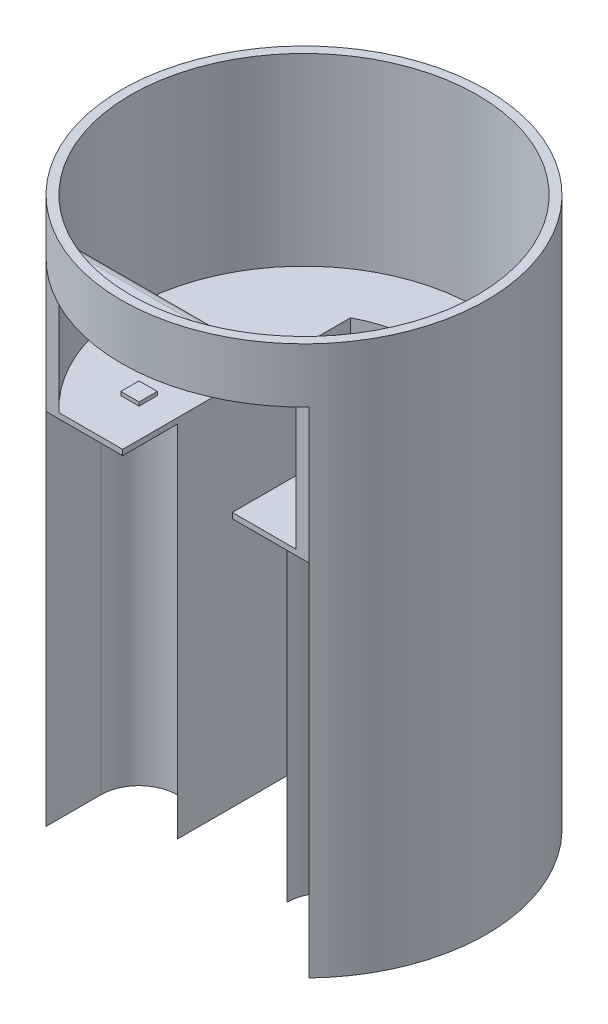
SolidWorks part; units mm, degrees
ref_plane "Front Plane" through (0, 0, 0) normal (0, 0, 1) x (1, 0, 0)
ref_plane "Top Plane" through (0, 0, 0) normal (0, 1, 0) x (1, 0, 0)
ref_plane "Right Plane" through (0, 0, 0) normal (1, 0, 0) x (0, 0, -1)
sketch "Sketch2" plane through (0, 0, 0) normal (0, 1, 0) x (1, 0, 0)
  line L0 (0.0632, -6.4631) -> (0.0632, -55.8981) construction
  line L1 (-29.9368, 95.4138) -> (-29.9368, -39.463)
  line L2 (30.0632, 95.374) -> (30.0632, -39.463)
  line L3 (-71.9368, -39.463) -> (-71.9368, -69.463)
  line L4 (72.0632, -39.463) -> (72.0632, -69.463)
  arc A0 (72.0632, -69.3317) -> (30.0632, 95.374) centre (0, 0) ccw
  arc A1 (-29.9368, -39.463) -> (-71.9368, -39.463) centre (-50.9368, -39.463) ccw
  arc A2 (30.0632, -39.463) -> (72.0632, -39.463) centre (51.0632, -39.463) cw
  arc A3 (-29.9368, 95.4138) -> (-71.9368, -69.463) centre (0, 0) ccw
  dimension "D1" = 100
  dimension "D5" = 42
  dimension "D2" = 30
  dimension "D3" = 164.8768
  dimension "D6" = 30
extrude "Boss-Extrude2" add sketch "Sketch2" along normal blind 200 contours L1 A3 L3 A1 | L2 A2 L4 A0 region at (-62.4571, 0, -19.5366) region at (62.5169, 0, -19.5555)
sketch "Sketch3" plane through (0, 200, 0) normal (0, 1, 0) x (1, 0, 0)
  line L0 (-71.9368, -69.463) -> (-29.9368, -69.463)
  line L1 (-29.9368, -69.463) -> (-29.9368, -39.463)
  line L3 (-55.9368, -34.463) -> (-45.9368, -34.463)
  line L4 (-55.9368, -34.463) -> (-55.9368, -44.463)
  line L5 (-55.9368, -44.463) -> (-45.9368, -44.463)
  line L6 (-45.9368, -34.463) -> (-45.9368, -44.463)
  line L7 (-55.9368, -34.463) -> (-45.9368, -44.463) construction
  line L8 (-55.9368, -44.463) -> (-45.9368, -34.463) construction
  point P3 (-50.9368, -39.463)
  line M7 (-71.9368, -69.463) -> (-71.9368, -39.463)
  arc M8 (-71.9368, -39.463) -> (-29.9368, -39.463) centre (-50.9368, -39.463) cw
  dimension "D1" = 10
extrude "Boss-Extrude3" add sketch "Sketch3" along direction (0, -1, 0) on the side against the normal blind 3 contours L0 L1 L3 L6 L5 L4 M8 M7 region at (-50.9368, 200, 46.3318)
sketch "Sketch4" plane through (0, 200, 0) normal (0, 1, 0) x (1, 0, 0)
  line L0 (72.0632, -69.3317) -> (30.0632, -69.3317)
  line L1 (30.0632, -39.463) -> (30.0632, -69.3317)
  line L3 (46.0632, -34.463) -> (56.0632, -34.463)
  line L4 (46.0632, -34.463) -> (46.0632, -44.463)
  line L5 (46.0632, -44.463) -> (56.0632, -44.463)
  line L6 (56.0632, -34.463) -> (56.0632, -44.463)
  line L7 (46.0632, -34.463) -> (56.0632, -44.463) construction
  line L8 (46.0632, -44.463) -> (56.0632, -34.463) construction
  point P1 (51.0632, -39.463)
  arc M6 (30.0632, -39.463) -> (72.0632, -39.463) centre (51.0632, -39.463) cw
  line M7 (72.0632, -39.463) -> (72.0632, -69.3317)
  dimension "D1" = 10
extrude "Boss-Extrude4" add sketch "Sketch4" against normal blind 3 contours L1 L0 L3 L6 L5 L4 M6 M7 region at (51.0632, 200, 46.263)
sketch "Sketch5" plane through (0, 200, 0) normal (0, 1, 0) x (1, 0, 0)
  line L1 (-55.9368, -34.463) -> (-45.9368, -34.463)
  line L2 (-55.9368, -34.463) -> (-55.9368, -44.463)
  line L3 (-55.9368, -44.463) -> (-45.9368, -44.463)
  line L4 (-45.9368, -34.463) -> (-45.9368, -44.463)
  line L5 (46.0632, -34.463) -> (56.0632, -34.463)
  line L6 (46.0632, -34.463) -> (46.0632, -44.463)
  line L7 (46.0632, -44.463) -> (56.0632, -44.463)
  line L8 (56.0632, -34.463) -> (56.0632, -44.463)
extrude "Boss-Extrude5" add sketch "Sketch5" along normal blind 2 separate body contours L8 L5 L6 L7 | L2 L1 L4 L3 region at (51.0632, 200, 39.463)
sketch "Sketch7" plane through (0, 200, 0) normal (0, 1, 0) x (1, 0, 0)
  line L0 (-29.9368, 95.4138) -> (-29.9368, 55.4328)
  line L2 (30.0632, 95.374) -> (30.0632, 55.3643)
  arc A0 (30.0632, 95.374) -> (-29.9368, 95.4138) centre (0, 0) ccw
  arc A1 (30.0632, 55.3643) -> (-29.9368, 55.4328) centre (0, 0) ccw
  dimension "D1" = 126
  dimension "D2" = 40.0097
  dimension "D3" = 39.981
extrude "Boss-Extrude6" add sketch "Sketch7" against normal up to surface (200 mm away) contours A1 L0 A0 L2 up to face at (-62.4289, 0, 5.0663)
sketch "Sketch8" plane through (0, 200, 0) normal (0, 1, 0) x (1, 0, 0)
  line L0 (-71.9368, -69.463) -> (-64.8066, -69.463)
  line L2 (72.0632, -69.3317) -> (64.947, -69.3317)
  arc A0 (72.0632, -69.3317) -> (-71.9368, -69.463) centre (0, 0) ccw
  arc A1 (64.947, -69.3317) -> (-64.8066, -69.463) centre (0, 0) ccw
  dimension "D1" = 7.1301
  dimension "D2" = 190
  dimension "D3" = 7.1163
extrude "Boss-Extrude7" add sketch "Sketch8" along normal blind 101 contours A1 L0 A0 L2
sketch "Sketch10" plane through (0, 301, 0) normal (0, 1, 0) x (1, 0, 0)
  line L0 (-71.9368, -69.463) -> (-64.8066, -69.463)
  line L1 (64.947, -69.3317) -> (72.0632, -69.3317)
  arc A0 (-71.9368, -69.463) -> (72.0632, -69.3317) centre (0, 0) ccw
  arc A1 (-64.8066, -69.463) -> (64.947, -69.3317) centre (0, 0) ccw
extrude "Boss-Extrude8" add sketch "Sketch10" against normal blind 15 contours A0 L1 A1 L0
sketch "Sketch11" plane through (0, 286, 0) normal (0, -1, 0) x (1, 0, 0)
  line L0 (-64.8066, 69.463) -> (64.947, 69.3317)
  line L3 (-71.9368, 69.463) -> (-64.8066, 69.463)
  line L4 (64.947, 69.3317) -> (72.0632, 69.3317)
  arc A3 (64.947, 69.3317) -> (-64.8066, 69.463) centre (0, 0) ccw
  arc A4 (72.0632, 69.3317) -> (-71.9368, 69.463) centre (0, 0) ccw
  arc A5 (64.947, 69.3317) -> (-64.8066, 69.463) centre (0, 0) ccw
  line M1 (-71.9368, 69.463) -> (-64.8066, 69.463)
  arc M2 (-64.8066, 69.463) -> (64.947, 69.3317) centre (0, 0) cw
  line M3 (64.947, 69.3317) -> (72.0632, 69.3317)
  arc M4 (72.0632, 69.3317) -> (-71.9368, 69.463) centre (0, 0) ccw
  dimension "D1" = 0
extrude "Boss-Extrude9" add sketch "Sketch11" along normal blind 15 contours M4 M1 M2 M3 | L0 M2 region at (0.0807, 286, 79.7667) region at (-68.3717, 286, 70.9353)
fillet "Fillet2" radius 6 1 edges at (0.0702, 286, 69.3973)
